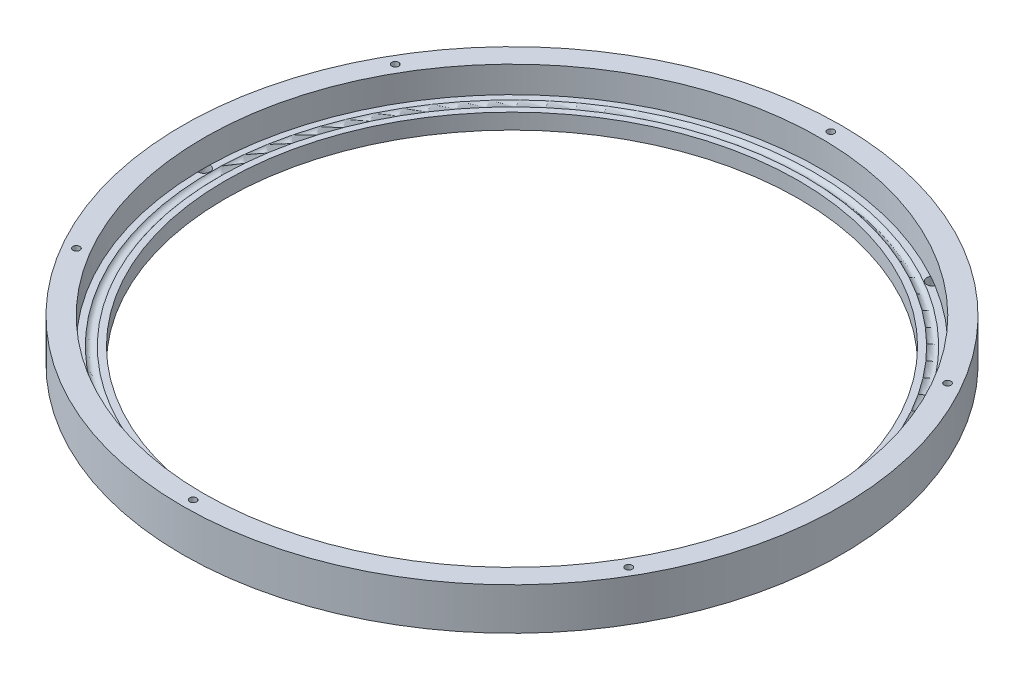
SolidWorks part; units mm, degrees
material "6061 Alloy"
ref_plane "Front Plane" through (0, 0, 0) normal (0, 0, 1) x (1, 0, 0)
ref_plane "Top Plane" through (0, 0, 0) normal (0, 1, 0) x (1, 0, 0)
ref_plane "Right Plane" through (0, 0, 0) normal (1, 0, 0) x (0, 0, -1)
sketch "Sketch1" plane through (0, 0, 0) normal (0, 1, 0) x (1, 0, 0)
  line L0 (50.3237, -87.1633) -> (0, 0) construction
  line L1 (0, 0) -> (0, -32.7983) construction
  circle A0 centre (0, 0) radius 93.6625
  circle A1 centre (0, 0) radius 107.6325
  circle A3 centre (0, 0) radius 100.6475
  circle A4 centre (0, -104.14) radius 1.1303
  circle A5 centre (50.3237, -87.1633) radius 1.9939
  circle A6 centre (50.3237, -87.1633) radius 5.588
  dimension "D1" = 187.325
  dimension "D5" = 2.2606
  dimension "D7" = 3.9878
  dimension "D9" = 11.176
  dimension "D4" = 104.14
  dimension "D6" = 100.6475
  dimension "D8" = 30
  dimension "D2" = 13.97
  dimension "D3" = 6.985
extrude "Boss-Extrude1" add sketch "Sketch1" along normal blind 5.08 contours A3 A0 | A1 A4 A3 | A3 A6 A5 | A3 A6 A5 region at (-104.5882, 0, 0) region at (86.0228, 0, 46.5303) region at (49.01, 0, 84.8879) region at (51.604, 0, 89.3808)
extrude "Boss-Extrude3" add sketch "Sketch1<3>" along normal blind 8.636 from surface contours A1 A4 A3 | A3 A5 | A3 A6 A5 region at (-104.5882, 0, 0) region at (51.604, 0, 89.3808) region at (50.7451, 0, 87.8931) starting at face at (50.3237, 5.08, 89.1572)
sketch "Sketch1<3>" plane through (0, 0, 0) normal (0, 1, 0) x (1, 0, 0) same geometry as "Sketch1"
pattern_circular "CirPattern1" count 6 over 360 about axis through (0, 13.716, 0) along (0, 1, 0) of face at (0, 0, 105.2703)
sketch "Sketch2" plane through (0, 0, 0) normal (1, 0, 0) x (0, 0, -1)
  line L0 (-93.6625, 0) -> (93.6625, 0) construction
  line L1 (93.6625, 5.08) -> (-93.6625, 5.08) construction
  line L2 (-93.6625, 0) -> (93.6625, 0)
  line L3 (93.6625, 5.08) -> (-93.6625, 5.08)
  line L4 (91.6697, 4.318) -> (97.1828, 4.318) construction
  line L5 (0, 5.08) -> (0, 35.8369)
  circle A0 centre (97.155, 5.9055) radius 1.5875 construction
  circle A1 centre (97.155, 5.969) radius 1.651
  dimension "D2" = 3.175
  dimension "D4" = 3.302
  dimension "D1" = 97.155
  dimension "D3" = 0.762
revolve "Cut-Revolve2" cut sketch "Sketch2" angle 360 about L5
extrude "Cut-Extrude2" cut sketch "Sketch1<4>" along normal blind 0.635 contours A3 A6 A5 | A3 A6 A5 region at (49.01, 0, 84.8879) region at (51.604, 0, 89.3808)
sketch "Sketch1<4>" plane through (0, 0, 0) normal (0, 1, 0) x (1, 0, 0) same geometry as "Sketch1"
pattern_circular "CirPattern3" count 3 over 360 about axis through (0, 0, 0) along (0, 1, 0) of face at (50.3237, 0.635, 89.1572) of face at (50.8222, 5.08, 88.0267) of face at (50.3237, 0.635, 89.1572) of face at (50.3237, 0.635, 92.7513)
equation "\"Middle Coupler Inner Daimeter\"= 6.75in"
equation "\"Middle Coupler  Wall Thickness\" = 0.25in"
equation "\"Middle Coupler Bottom Thickness\"= 0.2in"
equation "\"Bearing Rail Offset\"= 0.45in"
equation "\"3-56 UNF Tap\"= 0.089in"
equation "\"3-56 UNF Clearance\"= 0.104in"
equation "\"Ball Bearing Distance\"= 0.03in"
equation "\"D1@Sketch1\"=\"Middle Coupler Inner Daimeter\"+0.625in"
equation "\"D3@Sketch1\"=\"D2@Sketch1\"/2"
equation "\"D4@Sketch1\"=(\"D1@Sketch1\"+\"D3@Sketch1\"+\"D2@Sketch1\")/2"
equation "\"D5@Sketch1\"=\"3-56 UNF Tap\""
equation "\"D1@Sketch2\"=\"Middle Coupler Inner Daimeter\"/2in + \"Bearing Rail Offset\""
equation "\"D3@Sketch2\"=\"Ball Bearing Distance\""
equation "\"D4@Sketch2\"=\"D2@Sketch2\"+0.005"
equation "\"D1@Boss-Extrude3\"=0.330in+0.01in"
equation "\"D6@Sketch1\"=(\"D1@Sketch1\"/2+\"D3@Sketch1\")"
equation "\"TCA Outer Diameter\" = 8.625in"
equation "\"Interstage Aeroframe Wall Thickness\" = 0.072in"
equation "\"Compression Spring OD\"= 0.42in"
equation "\"10-24 Tap\"= 0.157in"
equation "\"10-24 Clearance\"= 0.196in"
